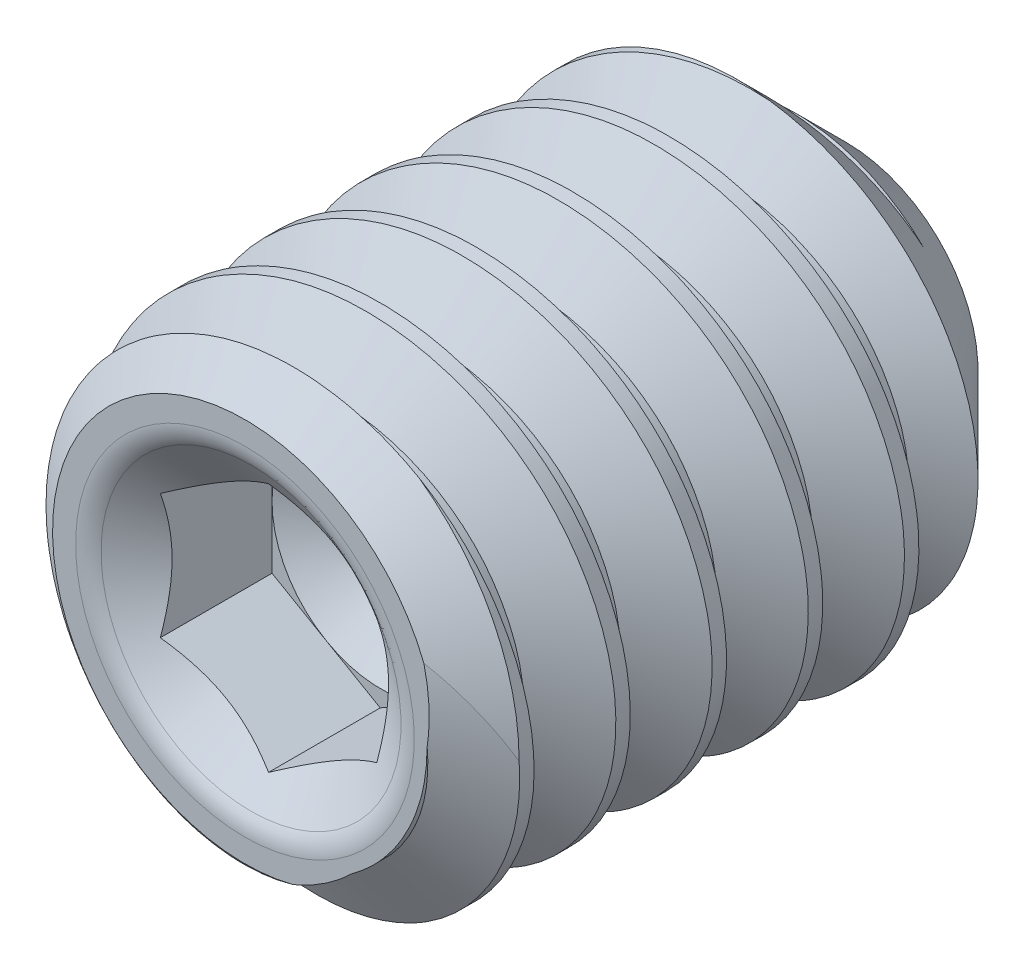
SolidWorks part; units mm, degrees
ref_plane "Front" through (0, 0, 0) normal (0, 0, 1) x (1, 0, 0)
ref_plane "Top" through (0, 0, 0) normal (0, 1, 0) x (1, 0, 0)
ref_plane "Right" through (0, 0, 0) normal (1, 0, 0) x (0, 0, -1)
sketch "Sketch22" plane through (0, 0, 0) normal (1, 0, 0) x (0, 0, -1)
  line L0 (-1.0854, 0) -> (-1.0854, 0.8)
  line L1 (-1.0854, 0.8) -> (-0.9453, 1)
  line L2 (-0.9453, 1) -> (0.9626, 1)
  line L3 (0.9626, 1) -> (1.4146, 0.548)
  line L4 (1.4146, 0.548) -> (1.0854, 0)
  line L5 (1.0854, 0) -> (-1.0854, 0)
  line L6 (1.0854, 0) -> (1.4146, 0) construction
  line L7 (1.4146, 0) -> (1.4146, 0.548) construction
  line L8 (1.4146, -0.548) -> (1.0854, 0) construction
  line L9 (-0.9453, -1) -> (0.9626, -1) construction
  dimension "Dia" = 2
  dimension "Length" = 2.5
  dimension "D3" = 35
  dimension "D5" = 118
  dimension "D6" = 45
  dimension "D7" = 1.6
revolve "Revolve1" add sketch "Sketch22" angle 360 about L6
ref_plane "Plane1" through (0, 0, -1.4146) normal (0, 0, 1) x (1, 0, 0)
sketch "Sketch27" plane through (0, 0, -1.4146) normal (0, 0, 1) x (1, 0, 0)
  circle A0 centre (0, 0) radius 1 construction
  circle A1 centre (0, 0) radius 1
curve "Helix/Spiral1" pitch 0.4 height 2.9 radius 1 centre (0, 0, -1.4146) axis (0, 0, 1) start towards (0, 1, 0)
sketch "Sketch28" plane through (0, 0, 0) normal (1, 0, 0) x (0, 0, -1)
  line L0 (1.4146, 1) -> (1.7546, 1)
  line L1 (1.7546, 1) -> (1.6146, 0.7575)
  line L2 (1.6146, 0.7575) -> (1.5546, 0.7575)
  line L3 (1.5546, 0.7575) -> (1.4146, 1)
  line L4 (1.4846, 0.8788) -> (1.6846, 0.8788) construction
  line L6 (-0.9453, 1) -> (0.9626, 1) construction
  dimension "D1" = 0.06
  dimension "D2" = 0.2
  dimension "D3" = 60
sweep "Cut-Sweep2" cut profiles "Sketch28" path "Helix/Spiral1"
sketch "Sketch23" plane through (0, 0, 1.0854) normal (0, 0, 1) x (1, 0, 0)
  line L1 (0, 0.5196) -> (-0.45, 0.2598)
  line L2 (-0.45, 0.2598) -> (-0.45, -0.2598)
  line L3 (-0.45, -0.2598) -> (0, -0.5196)
  line L4 (0, -0.5196) -> (0.45, -0.2598)
  line L5 (0.45, -0.2598) -> (0.45, 0.2598)
  line L6 (0.45, 0.2598) -> (0, 0.5196)
  circle A0 centre (0, 0) radius 0.45 construction
  dimension "Hex" = 0.9
extrude "Cut-Extrude10" cut sketch "Sketch23" against normal blind 0.5625
sketch "Sketch24" plane through (0, 0, 1.0854) normal (0, 0, 1) x (1, 0, 0)
  line L0 (0, 0.5196) -> (0, 0.8) construction
  circle A0 centre (0, 0) radius 0.6598
  point P5 (0, 0.6598)
  dimension "D1" = 0.1402
extrude "Cut-Extrude11" cut sketch "Sketch24" against normal through all draft 55
sketch "Sketch26" plane through (0, 0, 0.5229) normal (0, 0, 1) x (1, 0, 0)
  circle A0 centre (0, 0) radius 0.45 construction
  circle A1 centre (0, 0) radius 0.45
extrude "Cut-Extrude12" cut sketch "Sketch26" against normal through all draft 60
sketch "Sketch30" plane through (0, 0, 0) normal (1, 0, 0) x (0, 0, -1)
  line L0 (-0.9453, 1) -> (0.9626, 1) construction
  line L1 (-1.0854, 0) -> (-1.0854, 0.8) construction
  line L2 (1.4146, 0) -> (1.4146, 0.548) construction
  line L3 (-0.9453, -1) -> (0.9626, -1) construction
  point P0 (-1.0854, 1)
  point P1 (1.4146, 1)
  point P2 (1.4146, -1)
  point P11 (0.4146, -1)
  dimension "D1" = 1
sketch "Sketch31" plane through (0, 0, 0) normal (1, 0, 0) x (0, 0, -1)
  line L2 (1.0854, 0) -> (1.4146, -0.548)
  line L3 (1.4146, 0.548) -> (1.0854, 0)
fillet "Fillet2" radius 0.1402 1 edges at (0.6598, 0, 1.0854)
equation "\"D7@Sketch22\"=\"Dia@Sketch22\"*.8"
equation "\"D1@Sketch28\" = \"D4@Helix/Spiral1\" * .15"
equation "\"D2@Sketch28\" = \"D4@Helix/Spiral1\" * .5"
equation "\"D3@Helix/Spiral1\" = \"Length@Sketch22\" + \"D4@Helix/Spiral1\""
equation "\"D1@Sketch30\" = \"D4@Helix/Spiral1\" * 2.5"
equation "\"hex Depth@Cut-Extrude10\" = \"Hex@Sketch23\" * .625"
equation "\"D1@Fillet2\" = \"D1@Sketch24\""
